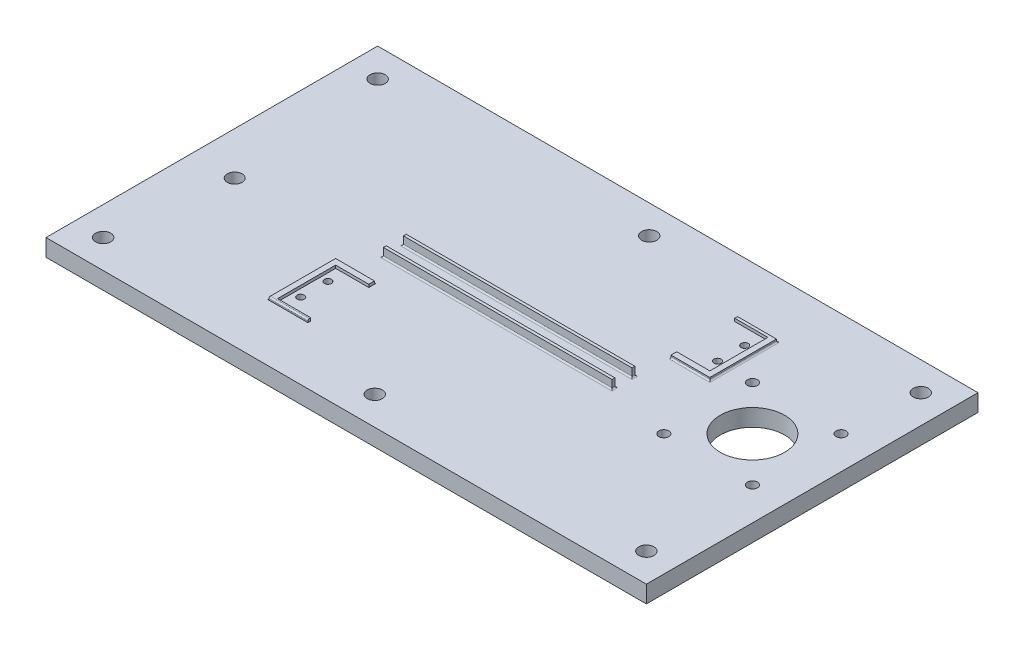
SolidWorks part; units mm, degrees
ref_plane "Front Plane" through (0, 0, 0) normal (0, 0, 1) x (1, 0, 0)
ref_plane "Top Plane" through (0, 0, 0) normal (0, 1, 0) x (1, 0, 0)
ref_plane "Right Plane" through (0, 0, 0) normal (1, 0, 0) x (0, 0, -1)
sketch "Sketch1" plane through (0, 0, 0) normal (0, 1, 0) x (1, 0, 0)
  line L0 (0, -55) -> (0, 55) construction
  line L1 (-105, -58) -> (105, -58)
  line L2 (-105, -58) -> (-105, 58)
  line L3 (-105, 58) -> (105, 58)
  line L4 (105, -58) -> (105, 58)
  line L5 (-105, -58) -> (105, 58) construction
  line L6 (-105, 58) -> (105, -58) construction
  line L7 (-55, 0) -> (55, 0) construction
  circle A0 centre (-95, 48) radius 2.65
  circle A1 centre (95, 48) radius 2.65
  circle A2 centre (95, -48) radius 2.65
  circle A3 centre (-95, -48) radius 2.65
  circle A4 centre (78, 6.11) radius 11.25
  circle A5 centre (93.5, 21.61) radius 1.75
  circle A6 centre (62.5, 21.61) radius 1.75
  circle A7 centre (62.5, -9.39) radius 1.75
  circle A8 centre (93.5, -9.39) radius 1.75
  circle A11 centre (-90, -7) radius 2.6
  circle A12 centre (0, 48) radius 2.65
  circle A13 centre (0, -48) radius 2.65
  point P0 (0, 0)
  dimension "D3" = 5.3
  dimension "D6" = 22.5
  dimension "D7" = 3.5
  dimension "D8" = 3.5
  dimension "D9" = 3.5
  dimension "D10" = 3.5
  dimension "D20" = 5.2
  dimension "D21" = 7
  dimension "D23" = 5.3
  dimension "D1" = 116
  dimension "D2" = 210
  dimension "D4" = 10
  dimension "D5" = 10
  dimension "D11" = 31
  dimension "D12" = 31
  dimension "D13" = 31
  dimension "D14" = 15.5
  dimension "D15" = 15.5
  dimension "D16" = 15.5
  dimension "D17" = 6.11
  dimension "D18" = 27
  dimension "D19" = 0
  dimension "D22" = 15
  dimension "D24" = 0
  dimension "D25" = 48
extrude "Boss-Extrude1" add sketch "Sketch1" along normal blind 6
sketch "Sketch4" plane through (0, 6, 0) normal (0, 1, 0) x (1, 0, 0)
  line L0 (105, 58) -> (-105, 58) construction
  line L1 (40.9, 37) -> (52.5, 37)
  line L3 (40.9, 16.7) -> (52.5, 16.7)
  line L4 (52.5, 37) -> (52.5, 16.7)
  line L5 (-105, -58) -> (105, -58) construction
  line L6 (-45, -16.7) -> (-33.4, -16.7)
  line L7 (-45, -16.7) -> (-45, -37)
  line L8 (-45, -37) -> (-33.4, -37)
  line L10 (-105, 58) -> (-105, -58) construction
  line L12 (54.5, 38) -> (54.5, 14.7)
  line L15 (40.9, 38) -> (40.9, 37)
  line L17 (-47, -14.7) -> (-47, -38)
  line L20 (40.9, 16.7) -> (40.9, 14.7)
  line L21 (40.9, 38) -> (54.5, 38)
  line L22 (54.5, 14.7) -> (40.9, 14.7)
  line L23 (-33.4, -16.7) -> (-33.4, -14.7)
  line L24 (-33.4, -14.7) -> (-47, -14.7)
  line L25 (-33.4, -37) -> (-33.4, -38)
  line L26 (-33.4, -38) -> (-47, -38)
  circle A0 centre (62.5, 21.61) radius 1.75 construction
  circle A1 centre (49.9, 31.5) radius 1.25
  circle A2 centre (49.9, 22) radius 1.25
  circle A3 centre (-42.4, -22) radius 1.25
  circle A4 centre (-42.4, -31.5) radius 1.25
  dimension "D3" = 10
  dimension "D5" = 2.5
  dimension "D6" = 2.5
  dimension "D13" = 2.5
  dimension "D14" = 2.5
  dimension "D1" = 20.3
  dimension "D2" = 11.6
  dimension "D4" = 21
  dimension "D7" = 9.5
  dimension "D8" = 5.3
  dimension "D9" = 2.6
  dimension "D10" = 21
  dimension "D11" = 20.3
  dimension "D12" = 11.6
  dimension "D15" = 9.5
  dimension "D16" = 5.3
  dimension "D17" = 2.6
  dimension "D18" = 60
  dimension "D21" = 2
  dimension "D26" = 2
extrude "Cut-Extrude1" cut sketch "Sketch4" against normal blind 5.5 contours A1 | A2
extrude "Boss-Extrude3" add sketch "Sketch4<3>" along normal blind 1 contours L1 L4 L3 L20 L22 L12 L21 L15
sketch "Sketch4<3>" plane through (0, 6, 0) normal (0, 1, 0) x (1, 0, 0) same geometry as "Sketch4"
extrude "Boss-Extrude4" add sketch "Sketch4<4>" along normal blind 1 contours L24 L17 L26 L25 L8 L7 L6 L23
sketch "Sketch4<4>" plane through (0, 6, 0) normal (0, 1, 0) x (1, 0, 0) same geometry as "Sketch4"
extrude "Cut-Extrude2" cut sketch "Sketch4<5>" against normal blind 5.5 contours A3 | A4
sketch "Sketch4<5>" plane through (0, 6, 0) normal (0, 1, 0) x (1, 0, 0) same geometry as "Sketch4"
sketch "Sketch6" plane through (0, 6, 0) normal (0, 1, 0) x (1, 0, 0)
  line L1 (-40, 3) -> (40, 3)
  line L2 (-40, 3) -> (-40, 2)
  line L3 (-40, 2) -> (40, 2)
  line L4 (40, 3) -> (40, 2)
  line L5 (-40, -5) -> (40, -5)
  line L6 (-40, -5) -> (-40, -4)
  line L7 (-40, -4) -> (40, -4)
  line L8 (40, -5) -> (40, -4)
  point P10 (0, 2)
  dimension "D1" = 1
  dimension "D2" = 80
  dimension "D3" = 2
  dimension "D4" = 6
extrude "Boss-Extrude5" add sketch "Sketch6" along normal blind 3
fillet "Fillet1" radius 0.5 14 edges at (54.5, 6, -26.35) (40, 6, -2.5) (40, 6, 4.5) (0, 6, -2) (0, 6, -3) (-40, 6, -2.5) (0, 6, 4) (-40, 6, 4.5) (0, 6, 5) (-47, 6, 26.35) (47.7, 6, -38) (47.7, 6, -14.7) (-40.2, 6, 14.7) (-40.2, 7, 38)
